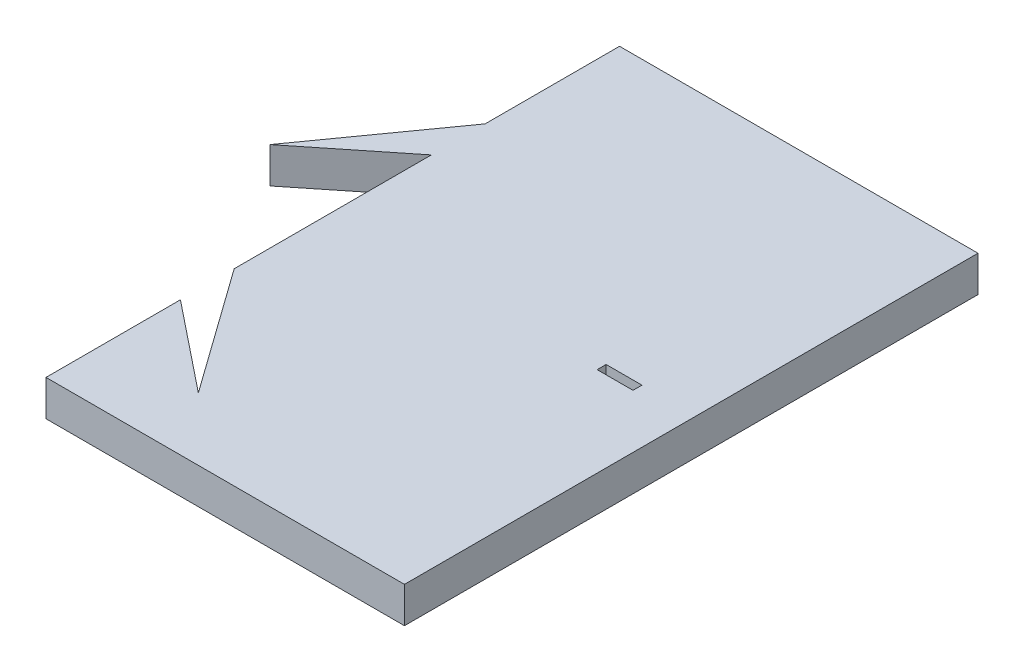
SolidWorks part; units mm, degrees
ref_plane "Front Plane" through (0, 0, 0) normal (0, 0, 1) x (1, 0, 0)
ref_plane "Top Plane" through (0, 0, 0) normal (0, 1, 0) x (1, 0, 0)
ref_plane "Right Plane" through (0, 0, 0) normal (1, 0, 0) x (0, 0, -1)
sketch "Sketch1" plane through (0, 0, 0) normal (0, 1, 0) x (1, 0, 0)
  line L0 (0, 75) -> (50, 35)
  line L1 (0, 0) -> (200, 0)
  line L2 (0, 0) -> (0, 75)
  line L3 (0, 320) -> (200, 320)
  line L4 (200, 0) -> (200, 320)
  line L5 (50, 35) -> (0, 105)
  line L6 (0, 215) -> (-50, 175)
  line L7 (-50, 175) -> (0, 245)
  line L8 (0, 245) -> (0, 320)
  line L9 (0, 105) -> (0, 215)
  dimension "D1" = 200
  dimension "D2" = 320
  dimension "D3" = 75
  dimension "D4" = 40
  dimension "D6" = 40
  dimension "D7" = 75
  dimension "D8" = 50
  dimension "D9" = 110
  dimension "D10" = 30
  dimension "D11" = 50
extrude "Boss-Extrude1" add sketch "Sketch1" along normal blind 20
sketch "Sketch2" plane through (0, 0, 0) normal (0, -1, 0) x (1, 0, 0)
  line L1 (170, -162.5) -> (150, -162.5)
  line L2 (170, -162.5) -> (170, -157.5)
  line L3 (170, -157.5) -> (150, -157.5)
  line L4 (150, -162.5) -> (150, -157.5)
  line L5 (200, 0) -> (200, -320) construction
  line L6 (0, 0) -> (200, 0) construction
  dimension "D1" = 30
  dimension "D2" = 157.5
  dimension "D3" = 5
  dimension "D4" = 20
extrude "Cut-Extrude1" cut sketch "Sketch2" against normal through all
